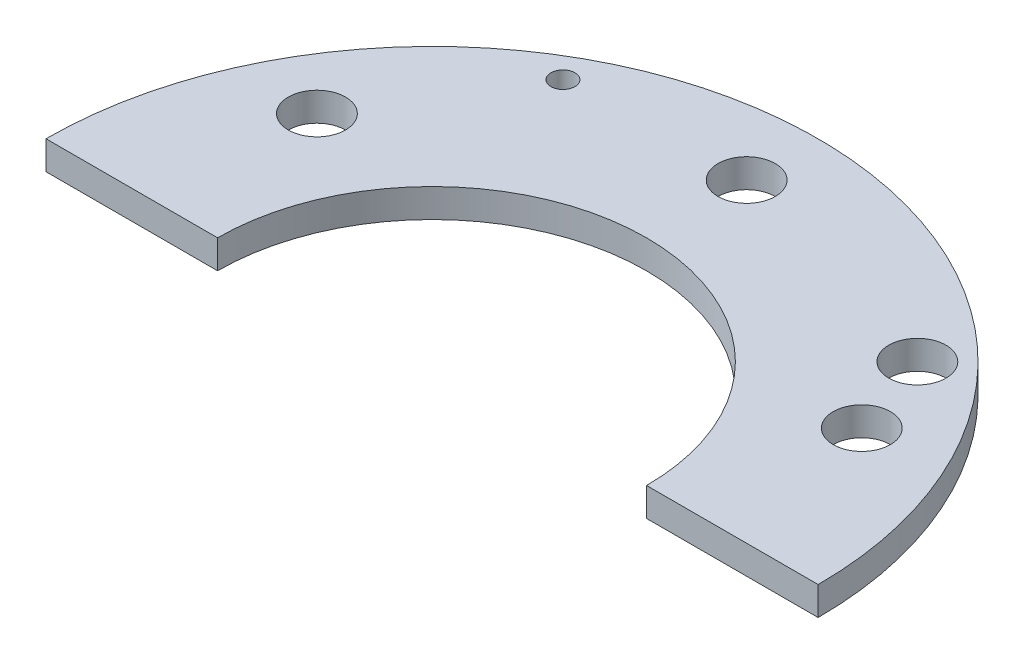
SolidWorks part; units mm, degrees
material "ABS"
ref_plane "Front Plane" through (0, 0, 0) normal (0, 0, 1) x (1, 0, 0)
ref_plane "Top Plane" through (0, 0, 0) normal (0, 1, 0) x (1, 0, 0)
ref_plane "Right Plane" through (0, 0, 0) normal (1, 0, 0) x (0, 0, -1)
sketch "Sketch1" plane through (0, 0, 0) normal (0, 1, 0) x (1, 0, 0)
  circle A0 centre (0, 0) radius 13.5
  dimension "D1" = 27
extrude "Boss-Extrude1" add sketch "Sketch1" along normal blind 1
sketch "Sketch19" plane through (0, 1, 0) normal (0, 1, 0) x (1, 0, 0)
  circle A0 centre (0, 11) radius 1
  circle A1 centre (9.5263, 5.5) radius 1
  circle A2 centre (9.5263, -5.5) radius 1
  circle A3 centre (0, -11) radius 1
  circle A4 centre (-9.5263, -5.5) radius 1
  circle A5 centre (-9.5263, 5.5) radius 1
  point P13 (0, 0)
  dimension "D1" = 2
  dimension "D2" = 11
  dimension "D3" = 6
extrude "Cut-Extrude1" cut sketch "Sketch19" against normal through all both and the other way through all
sketch "Sketch20" plane through (0, 1, 0) normal (0, 1, 0) x (1, 0, 0)
  circle A0 centre (0, 0) radius 7.5
  dimension "D1" = 15
extrude "Cut-Extrude2" cut sketch "Sketch20" against normal through all both and the other way through all
sketch "Sketch21" plane through (0, 0, 0) normal (0, 0, 1) x (1, 0, 0)
  line L1 (-36.7533, 32.3113) -> (29.1209, 32.3113)
  line L2 (-36.7533, 32.3113) -> (-36.7533, -19.668)
  line L3 (-36.7533, -19.668) -> (29.1209, -19.668)
  line L4 (29.1209, 32.3113) -> (29.1209, -19.668)
extrude "Cut-Extrude3" cut sketch "Sketch21" along normal through all
sketch "Sketch22" plane through (0, 1, 0) normal (0, 1, 0) x (1, 0, 0)
  line L0 (-9.5263, 5.5) -> (0, 11)
  line L1 (0, 0) -> (-6.25, 10.8253) construction
  circle A0 centre (-6.25, 10.8253) radius 0.42
  dimension "D1" = 0.84
  dimension "D2" = 12.5
extrude "Cut-Extrude4" cut sketch "Sketch22" against normal through all both and the other way through all contours A0 | A0 L1 | L1 A0 region at (-6.25, 1, -10.8253)
sketch "Sketch23" plane through (0, 1, 0) normal (0, 1, 0) x (1, 0, 0)
  line L0 (0, 0) -> (-6.25, 10.8253) construction
  line L1 (-6.25, 10.8253) -> (0, 0) construction
  line L2 (0, 0) -> (12.508, 12.508) construction
  circle A0 centre (8.4853, 8.4853) radius 1
  dimension "D1" = 2
  dimension "D2" = 12
  dimension "D3" = 75
extrude "Cut-Extrude5" cut sketch "Sketch23" against normal through all both and the other way through all
